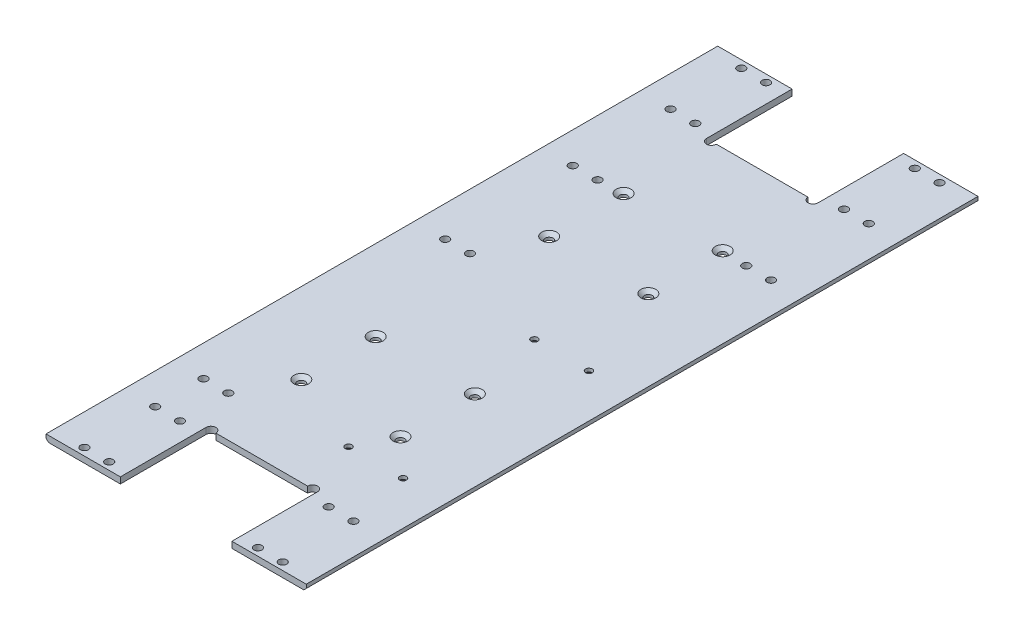
SolidWorks part; units mm, degrees
ref_plane "前视基准面" through (0, 0, 0) normal (0, 0, 1) x (1, 0, 0)
ref_plane "上视基准面" through (0, 0, 0) normal (0, 1, 0) x (1, 0, 0)
ref_plane "右视基准面" through (0, 0, 0) normal (1, 0, 0) x (0, 0, -1)
sketch "草图1" plane through (0, 0, 0) normal (0, 1, 0) x (1, 0, 0)
  line L6 (-52.5, -135.5) -> (52.5, -135.5)
  line L7 (52.5, -135.5) -> (52.5, 135.5)
  line L8 (-52.5, 135.5) -> (52.5, 135.5)
  line L9 (-52.5, -135.5) -> (-52.5, 135.5)
  point P8 (-50, 0)
extrude "凸台-拉伸1" add sketch "草图1" along normal blind 2.5
sketch "草图2" plane through (0, 2.5, 0) normal (0, 1, 0) x (1, 0, 0)
  circle A14 centre (35, -3.95) radius 1.35
  circle A15 centre (13, -3.95) radius 1.35
  circle A18 centre (35, -78.95) radius 1.35
  circle A19 centre (13, -78.95) radius 1.35
  circle A32 centre (20, -35) radius 1.6
  circle A33 centre (-20, -35) radius 1.6
  circle A34 centre (20, -65) radius 1.6
  circle A35 centre (-20, -65) radius 1.6
  circle A36 centre (-20, 35) radius 1.6
  circle A37 centre (20, 35) radius 1.6
  circle A40 centre (-20, 65) radius 1.6
  circle A41 centre (20, 65) radius 1.6
extrude "切除-拉伸1" cut sketch "草图2" against normal blind 10
sketch "草图7" plane through (0, 2.5, 0) normal (0, 1, 0) x (1, 0, 0)
  line L0 (0, -1.375) -> (0, 1.375) construction
  circle A0 centre (-40, 64.5) radius 1.6
  circle A1 centre (-30, 64.5) radius 1.6
  circle A2 centre (30, 64.5) radius 1.6
  circle A3 centre (40, 64.5) radius 1.6
chamfer "倒角3" distance 1.15 angle 45 4 edges at (13, 0, 2.6) (35, 0, 2.6) (35, 0, 77.6) (13, 0, 77.6)
chamfer "倒角4" distance 1.4 angle 45 8 edges at (-20, 2.5, 63.4) (-20, 2.5, 33.4) (20, 2.5, 66.6) (20, 2.5, 36.6) (-20, 2.5, -33.4) (-20, 2.5, -63.4) (20, 2.5, -36.6) (20, 2.5, -66.6)
chamfer "倒角5" distance 1 angle 45 2 edges at (52.5, 0, 0) (-52.5, 0, 0)
sketch "草图4" plane through (0, 0, 0) normal (0, -1, 0) x (1, 0, 0)
  line L0 (1.375, 0) -> (-1.375, 0) construction
  line L1 (-51.5, 135.5) -> (51.5, 135.5) construction
  line L2 (0, 100.95) -> (22.5, 100.95)
  line L3 (22.5, 100.95) -> (22.5, 135.5)
  line L4 (22.5, 135.5) -> (-22.5, 135.5)
  line L5 (-22.5, 135.5) -> (-22.5, 100.95)
  line L6 (-22.5, 100.95) -> (0, 100.95)
  line L7 (-22.5, -100.95) -> (0, -100.95)
  line L8 (-22.5, -135.5) -> (-22.5, -100.95)
  line L9 (22.5, -135.5) -> (-22.5, -135.5)
  line L10 (22.5, -100.95) -> (22.5, -135.5)
  line L11 (0, -100.95) -> (22.5, -100.95)
extrude "切除-拉伸2" cut sketch "草图4" against normal blind 10
sketch "草图6" plane through (0, 0, 0) normal (0, -1, 0) x (1, 0, 0)
  line L0 (0, -1.375) -> (0, 1.375) construction
  line L2 (1.375, 0) -> (-1.375, 0) construction
  circle A0 centre (-40, 132.5) radius 1.6
  circle A1 centre (-30, 132.5) radius 1.6
  circle A2 centre (-30, 103.95) radius 1.6
  circle A3 centre (-40, 103.95) radius 1.6
  circle A4 centre (40, 103.95) radius 1.6
  circle A5 centre (30, 103.95) radius 1.6
  circle A6 centre (30, 132.5) radius 1.6
  circle A7 centre (40, 132.5) radius 1.6
  circle A8 centre (40, -132.5) radius 1.6
  circle A9 centre (30, -132.5) radius 1.6
  circle A10 centre (30, -103.95) radius 1.6
  circle A11 centre (40, -103.95) radius 1.6
  circle A12 centre (-40, -103.95) radius 1.6
  circle A13 centre (-30, -103.95) radius 1.6
  circle A14 centre (-30, -132.5) radius 1.6
  circle A15 centre (-40, -132.5) radius 1.6
extrude "切除-拉伸3" cut sketch "草图6" against normal blind 10
extrude "切除-拉伸4" cut sketch "草图7" against normal blind 10
sketch "草图8" plane through (0, 0, 0) normal (0, -1, 0) x (1, 0, 0)
  line L4 (-40, 132.5) -> (-30, 132.5)
  circle A1 centre (-40, 84.45) radius 1.6
  circle A2 centre (-30, 84.45) radius 1.6
  circle A3 centre (-40, -13.05) radius 1.6
  circle A4 centre (-30, -13.05) radius 1.6
extrude "切除-拉伸5" cut sketch "草图8" against normal blind 10 contours A1 | A2 | A4 | A3 region at (-40, 0, 84.45)
sketch "草图9" plane through (0, 0, 0) normal (0, -1, 0) x (1, 0, 0)
  line L0 (0, -1.375) -> (0, 1.375) construction
  line L1 (1.375, 0) -> (-1.375, 0) construction
  line L2 (-22.5, 100.95) -> (22.5, 100.95) construction
  circle A3 centre (20.5, 100.95) radius 2
  circle A4 centre (-20.5, 100.95) radius 2
  circle A5 centre (-20.5, -100.95) radius 2
  circle A6 centre (20.5, -100.95) radius 2
  point P7 (22.4055, 102.95)
  point P15 (20.4245, 100.95)
  point P18 (0, 0)
extrude "切除-拉伸6" cut sketch "草图9" against normal blind 10
